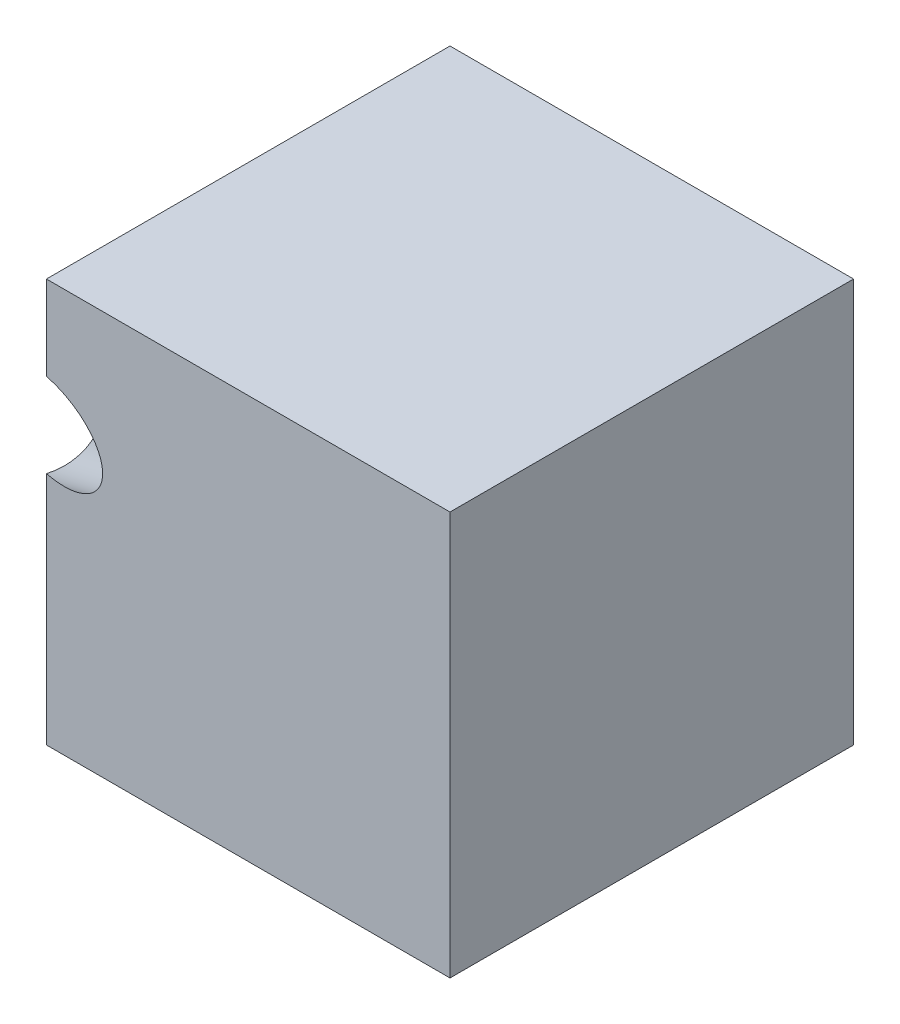
SolidWorks part; units mm, degrees
material "6061 Alloy"
ref_plane "Front Plane" through (0, 0, 0) normal (0, 0, 1) x (1, 0, 0)
ref_plane "Top Plane" through (0, 0, 0) normal (0, 1, 0) x (1, 0, 0)
ref_plane "Right Plane" through (0, 0, 0) normal (1, 0, 0) x (0, 0, -1)
sketch "Square" plane through (0, 0, 0) normal (0, 0, 1) x (1, 0, 0)
  line L1 (-25.4, -25.4) -> (25.4, -25.4)
  line L2 (-25.4, -25.4) -> (-25.4, 25.4)
  line L3 (-25.4, 25.4) -> (25.4, 25.4)
  line L4 (25.4, -25.4) -> (25.4, 25.4)
  line L5 (-25.4, -25.4) -> (25.4, 25.4) construction
  line L6 (-25.4, 25.4) -> (25.4, -25.4) construction
  point P0 (0, 0)
  dimension "D1" = 50.8
extrude "Cube-Extrusion" add sketch "Square" along normal blind 50.8
ref_plane "StickPlane" through (-28.2222, 14.1111, 28.2222) normal (0.6667, -0.3333, -0.6667) x (-0.7454, -0.2981, -0.5963)
sketch "Stick-Hole" plane through (-28.2222, 14.1111, 28.2222) normal (0.6667, -0.3333, -0.6667) x (-0.7454, -0.2981, -0.5963)
  line L0 (-18.932, 0) -> (-3.7864, -45.4369) construction
  circle A0 centre (-14.1886, -14.2302) radius 5
  point P2 (0, 0)
  dimension "D2" = 10
  dimension "D1" = 15
extrude "Stick-Cut" cut sketch "Stick-Hole" against normal through all from offset 5
